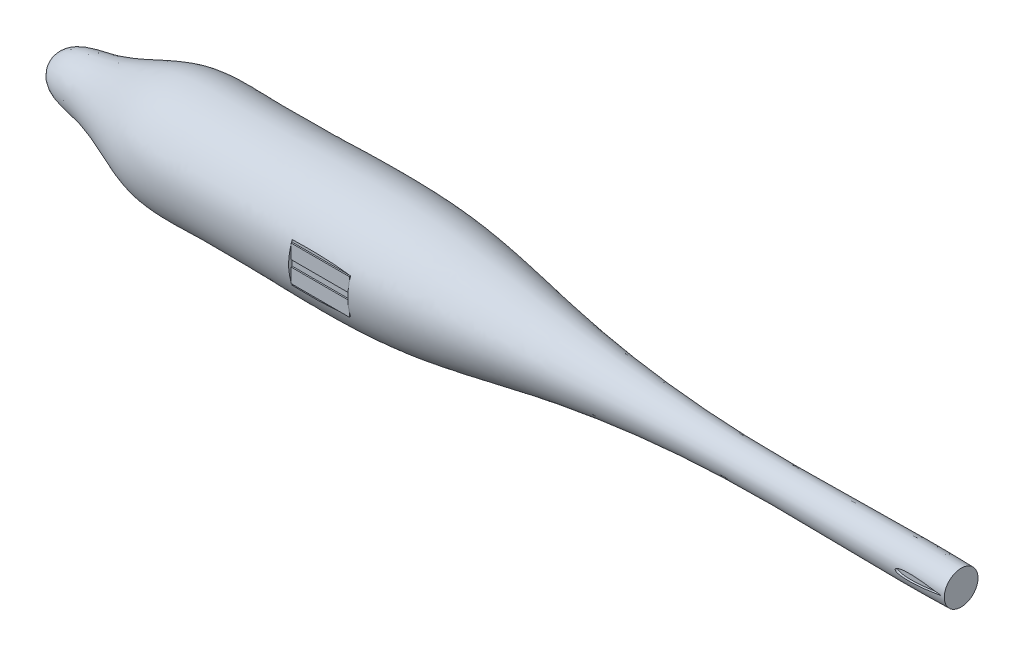
SolidWorks part; units mm, degrees
material "EPP"
ref_plane "Front Plane" through (0, 0, 0) normal (0, 0, 1) x (1, 0, 0)
ref_plane "Top Plane" through (0, 0, 0) normal (0, 1, 0) x (1, 0, 0)
ref_plane "Right Plane" through (0, 0, 0) normal (1, 0, 0) x (0, 0, -1)
sketch "Sketch1" plane through (0, 0, 0) normal (0, 0, 1) x (1, 0, 0)
  line L1 (1400, 97.6339) -> (0, 97.6339) construction
  line L3 (0, 0) -> (1400, 0) construction
  line L6 (1400, 0) -> (1400, 25.997)
  line L7 (0, 0) -> (12.8869, 0)
  line L8 (1388.532, 14.96) -> (1387.1201, 0)
  line L9 (1387.1201, 0) -> (1400, 0)
  spline S0 degree 3 poles (0, 0) (6.0079, 35.1205) (87.5704, 35.98) (174.2855, 89.8849) (355.2298, 80.4635) (551.199, 98.1903) (802.5668, 43.0656) (1072.4121, 17.7479) (1281.1497, 28.8593) (1400, 25.997) knots 0 0 0 0 0.060909 0.147322 0.213189 0.431417 0.561861 0.75012 1 1 1 1
  spline S1 degree 3 poles (12.8869, 0) (12.2702, 24.1237) (42.0071, 17.5904) (77.1548, 41.2159) (129.1678, 36.1628) (178.7554, 69.0831) (233.9908, 66.7109) (368.4506, 69.0999) (548.637, 76.3709) (801.0206, 37.1712) (1065.8549, -5.42) (1273.601, 25.8064) (1388.532, 14.96) knots 0 0 0 0 0.033016 0.050942 0.089125 0.13776 0.171792 0.205001 0.427814 0.55541 0.752934 1 1 1 1
  point P1 (1380.3069, 15.5522)
  point P18 (0, 0)
  point P23 (0, 0)
  point P25 (13.337, 0)
  point P27 (1387.1203, 0)
  dimension "D1" = 8
  dimension "D2" = 17.7948
revolve "Revolve2" add sketch "Sketch1" angle 360 about L3
ref_plane "Plane1" through (0, 0, 88) normal (0, 0, 1) x (1, 0, 0)
sketch "Sketch5" plane through (0, 0, 88) normal (0, 0, 1) x (1, 0, 0)
  line L0 (0, 0) -> (1400, 0) construction
  line L1 (450, 100) -> (540, 100)
  line L2 (450, 100) -> (450, -100)
  line L3 (450, -100) -> (540, -100)
  line L4 (540, 100) -> (540, -100)
  line L5 (450, 100) -> (540, -100) construction
  line L6 (450, -100) -> (540, 100) construction
  line L7 (1400, -25.997) -> (1400, 25.997) construction
  point P0 (495, 0)
  dimension "D1" = 450
  dimension "D2" = 90
  dimension "D3" = 200
sketch "Sketch7" plane through (0, 0, 88) normal (0, 0, 1) x (1, 0, 0)
  line L1 (1330.1015, 25) -> (1400.1015, 25)
  line L2 (1330.1015, 25) -> (1330.1015, -25)
  line L3 (1330.1015, -25) -> (1400.1015, -25)
  line L4 (1400.1015, 25) -> (1400.1015, -25)
  line L5 (1330.1015, 25) -> (1400.1015, -25) construction
  line L6 (1330.1015, -25) -> (1400.1015, 25) construction
  point P0 (1365.1015, 0)
extrude "Cut-Extrude4" cut sketch "Sketch5" against normal blind 6.5
sketch "Sketch8" plane through (0, 0, 81.5) normal (0, 0, 1) x (1, 0, 0)
  line L0 (450, 0) -> (540, 0) construction
  line L1 (450, 30.5883) -> (450, -30.5883) construction
  line L2 (540, 27.0452) -> (540, -27.0452) construction
  line L3 (540, -27.0452) -> (540, 27.0452) construction
  line L4 (450, 5) -> (540, 5)
  line L5 (450, 5) -> (450, -5)
  line L6 (450, -5) -> (540, -5)
  line L7 (540, 5) -> (540, -5)
  line L8 (450, 5) -> (540, -5) construction
  line L9 (450, -5) -> (540, 5) construction
  line L11 (540, -27.0452) -> (450, -27.0452)
  line L12 (540, -27.0452) -> (540, -5)
  line L13 (540, -5) -> (450, -5)
  line L14 (450, -27.0452) -> (450, -5)
  line L15 (540, 27.0452) -> (450, 27.0452)
  line L16 (540, 27.0452) -> (540, 5)
  line L17 (540, 5) -> (450, 5)
  line L18 (450, 27.0452) -> (450, 5)
  point P6 (495, 0)
  line M2 (450, 30.5883) -> (450, -30.5883)
  line M4 (540, -27.0452) -> (540, 27.0452)
  dimension "D1" = 10
  dimension "D2" = 22.0452
extrude "Boss-Extrude1" add sketch "Sketch8" along normal blind 2 contours L15 L4 M4 M2 | L11 L6 M4 M2 region at (495, 16.0226, 81.5) region at (495, -16.0226, 81.5)
curve "Curve4"
  spline degree 3 poles (1395, 0.1106, 88) (1393.8337, 0.3112, 88) (1391.503, 0.7122, 88) (1386.8387, 1.4577, 88) (1381.0079, 2.3135, 88) (1374.0074, 3.2252, 88) (1367.0075, 4.0161, 88) (1360.0075, 4.6625, 88) (1353.0064, 5.1217, 88) (1347.1673, 5.2834, 88) (1342.498, 5.2197, 88) (1338.9941, 5.0466, 88) (1335.4854, 4.7134, 88) (1332.5643, 4.2469, 88) (1330.2314, 3.6922, 88) (1328.4601, 3.1359, 88) (1326.971, 2.4608, 88) (1325.6343, 1.5675, 88) (1324.5974, 0, 88) (1325.6343, -1.5675, 88) (1326.971, -2.4608, 88) (1328.4601, -3.1359, 88) (1330.2314, -3.6922, 88) (1332.5643, -4.2469, 88) (1335.4854, -4.7134, 88) (1338.9941, -5.0466, 88) (1342.498, -5.2197, 88) (1347.1673, -5.2834, 88) (1353.0064, -5.1217, 88) (1360.0075, -4.6625, 88) (1367.0075, -4.0161, 88) (1374.0074, -3.2252, 88) (1381.0079, -2.3135, 88) (1386.8387, -1.4577, 88) (1391.503, -0.7122, 88) (1393.8337, -0.3112, 88) (1395, -0.1106, 88) knots 0 0 0 0 0.024684 0.04933 0.098522 0.147602 0.196578 0.24545 0.294219 0.342904 0.367241 0.391608 0.416059 0.440726 0.453243 0.466028 0.479473 0.486972 0.5 0.513028 0.520527 0.533972 0.546757 0.559274 0.583941 0.608392 0.632759 0.657096 0.705781 0.75455 0.803422 0.852398 0.901478 0.95067 0.975316 1 1 1 1
sketch "Sketch14" plane through (0, 0, 88) normal (0, 0, 1) x (1, 0, 0)
  line L0 (1395, 0.1106) -> (1395, -0.1106)
  spline S0 degree 3 poles (1950.8551, 1916.4205) (1541.7499, -55.83) (1468.1035, -11.5304) (1386.8387, 1.4577) (1381.0079, 2.3135) (1374.0074, 3.2252) (1367.0075, 4.0161) (1360.0075, 4.6625) (1353.0064, 5.1217) (1347.1673, 5.2834) (1342.498, 5.2197) (1338.9941, 5.0466) (1335.4854, 4.7134) (1332.5643, 4.2469) (1330.2314, 3.6922) (1328.4601, 3.1359) (1326.971, 2.4608) (1325.6343, 1.5675) (1324.5974, 0) (1325.6343, -1.5675) (1326.971, -2.4608) (1328.4601, -3.1359) (1330.2314, -3.6922) (1332.5643, -4.2469) (1335.4854, -4.7134) (1338.9941, -5.0466) (1342.498, -5.2197) (1347.1673, -5.2834) (1353.0064, -5.1217) (1360.0075, -4.6625) (1367.0075, -4.0161) (1374.0074, -3.2252) (1381.0079, -2.3135) (1386.8387, -1.4577) (1468.103, 11.5303) (1541.749, 55.8295) (1950.8476, -1916.3842) knots -1.618016 -1.618016 -1.618016 -1.618016 0.024684 0.04933 0.098522 0.147602 0.196578 0.24545 0.294219 0.342904 0.367241 0.391608 0.416059 0.440726 0.453243 0.466028 0.479473 0.486972 0.5 0.513028 0.520527 0.533972 0.546757 0.559274 0.583941 0.608392 0.632759 0.657096 0.705781 0.75455 0.803422 0.852398 0.901478 0.95067 0.975316 2.618006 2.618006 2.618006 2.618006 only from (1395, 0.1106) to (1395, -0.1106) construction
  spline S1 degree 3 poles (1395, 0.1106) (1393.8337, 0.3112) (1391.503, 0.7122) (1386.8387, 1.4577) (1381.0079, 2.3135) (1374.0074, 3.2252) (1367.0075, 4.0161) (1360.0075, 4.6625) (1353.0064, 5.1217) (1347.1673, 5.2834) (1342.498, 5.2197) (1338.9941, 5.0466) (1335.4854, 4.7134) (1332.5643, 4.2469) (1330.2314, 3.6922) (1328.4601, 3.1359) (1326.971, 2.4608) (1325.6343, 1.5675) (1324.5974, 0) (1325.6343, -1.5675) (1326.971, -2.4608) (1328.4601, -3.1359) (1330.2314, -3.6922) (1332.5643, -4.2469) (1335.4854, -4.7134) (1338.9941, -5.0466) (1342.498, -5.2197) (1347.1673, -5.2834) (1353.0064, -5.1217) (1360.0075, -4.6625) (1367.0075, -4.0161) (1374.0074, -3.2252) (1381.0079, -2.3135) (1386.8387, -1.4577) (1391.503, -0.7122) (1393.8337, -0.3112) (1395, -0.1106) knots 0 0 0 0 0.024684 0.04933 0.098522 0.147602 0.196578 0.24545 0.294219 0.342904 0.367241 0.391608 0.416059 0.440726 0.453243 0.466028 0.479473 0.486972 0.5 0.513028 0.520527 0.533972 0.546757 0.559274 0.583941 0.608392 0.632759 0.657096 0.705781 0.75455 0.803422 0.852398 0.901478 0.95067 0.975316 1 1 1 1
extrude "Cut-Extrude7" cut sketch "Sketch14" against normal blind 65
